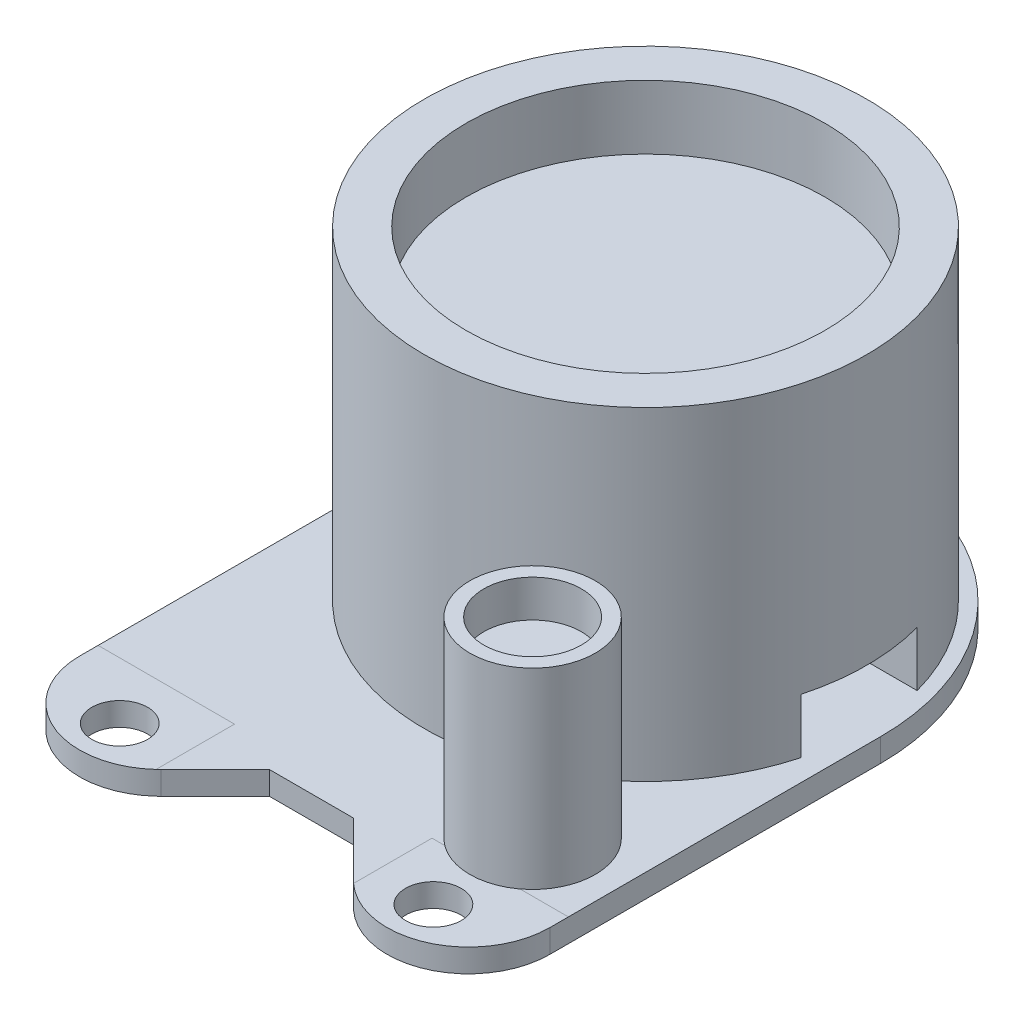
SolidWorks part; units mm, degrees
ref_plane "Front" through (0, 0, 0) normal (0, 0, 1) x (1, 0, 0)
ref_plane "Top" through (0, 0, 0) normal (0, 1, 0) x (1, 0, 0)
ref_plane "Right" through (0, 0, 0) normal (1, 0, 0) x (0, 0, -1)
sketch "Sketch1" plane through (0, 0, 0) normal (0, 1, 0) x (1, 0, 0)
  line L0 (-10.12, 0) -> (-10.12, -14.24)
  line L1 (10.12, 0) -> (10.12, -14.24)
  line L2 (-6.62, -17.74) -> (6.62, -17.74) construction
  line L3 (0, -0.8108) -> (0, -50000.8108) construction
  line L4 (-1.8103, -14.38) -> (1.8103, -14.38)
  line L5 (-4.1451, -16.7149) -> (-1.8103, -14.38)
  line L6 (1.8103, -14.38) -> (4.1451, -16.7149)
  arc A0 (10.12, 0) -> (-10.12, 0) centre (0, 0) ccw
  circle A1 centre (-6.75, -15.88) radius 1.2
  circle A2 centre (6.75, -15.88) radius 1.2
  arc A3 (-4.1451, -16.7149) -> (-10.12, -14.24) centre (-6.62, -14.24) cw
  arc A4 (4.1451, -16.7149) -> (10.12, -14.24) centre (6.62, -14.24) ccw
  point P14 (0, 0)
  point P19 (-6.1206, -18.7584)
  dimension "D1" = 20.24
  dimension "D2" = 27.86
  dimension "D3" = 2.4
  dimension "D4" = 13.5
  dimension "D7" = 26
  dimension "D6" = 0.66
  dimension "D8" = 3.5
  dimension "D9" = 3.5
  dimension "D5" = 24.5
  dimension "D10" = 45
extrude "Boss-Extrude1" add sketch "Sketch1" along normal blind 1
sketch "Sketch2" plane through (0, 1, 0) normal (0, 1, 0) x (1, 0, 0)
  line L0 (0, 0) -> (0, -50000) construction
  line L1 (0, 0) -> (50000, 0) construction
  line L3 (10.12, -14.24) -> (10.12, 0) construction
  line L4 (-4.25, -13.44) -> (-10.12, -13.44)
  line L5 (10.12, -14.24) -> (10.12, -13.44)
  line L6 (4.25, -13.44) -> (4.25, -16.8155)
  line L7 (4.25, -13.44) -> (10.12, -13.44)
  line L8 (-4.25, -13.44) -> (-4.25, -16.8155)
  line L9 (-10.12, -14.24) -> (-10.12, -13.44)
  arc A0 (4.1451, -16.7149) -> (10.12, -14.24) centre (6.62, -14.24) ccw construction
  arc A1 (4.25, -16.8155) -> (10.12, -14.24) centre (6.62, -14.24) ccw
  arc A2 (-4.25, -16.8155) -> (-10.12, -14.24) centre (-6.62, -14.24) cw
  dimension "D2" = 4.3
  dimension "D1" = 8.5
split line "Split Line1"
sketch "Sketch3" plane through (0, 0, 0) normal (0, -1, 0) x (1, 0, 0)
  line L0 (0, 0) -> (50000, 0) construction
  line L1 (0, 0) -> (3.75, 0) construction
  line L2 (0, 0) -> (2.6517, -2.6517) construction
  circle A0 centre (0, 0) radius 4.25
  circle A1 centre (0, 0) radius 3.75 construction
  circle A3 centre (3.75, 0) radius 0.15
  circle A4 centre (2.6517, -2.6517) radius 0.15
  circle A5 centre (0, -3.75) radius 0.15
  circle A6 centre (-2.6517, -2.6517) radius 0.15
  circle A7 centre (-3.75, 0) radius 0.15
  circle A8 centre (-2.6517, 2.6517) radius 0.15
  circle A9 centre (0, 3.75) radius 0.15
  circle A10 centre (2.6517, 2.6517) radius 0.15
  point P4 (0, 0)
  dimension "D1" = 8.5
  dimension "D2" = 7.5
  dimension "D3" = 0.3
  dimension "D5" = 45
  dimension "D4" = 8
split line "Split Line2"
sketch "Sketch4" plane through (0, 1, 0) normal (0, 1, 0) x (1, 0, 0)
  circle A0 centre (0, 0) radius 9.525
  circle A1 centre (0, 0) radius 7.725
  point P2 (0, 0)
  dimension "D1" = 19.05
  dimension "D2" = 1.8
extrude "Boss-Extrude2" add sketch "Sketch4" along normal blind 13.94 separate body
sketch "Sketch5" plane through (0, 0, 0) normal (1, 0, 0) x (0, 0, -1)
  line L0 (0, 11.4963) -> (0, -49988.5037) construction
  line L2 (0, 14.94) -> (0, 1) construction
  line L3 (-13.44, 1) -> (0, 1) construction
  line L4 (-2.5, 1) -> (2.5, 1)
  line L5 (-2.5, 1) -> (-2.5, 3.36)
  line L6 (-2.5, 3.36) -> (2.5, 3.36)
  line L7 (2.5, 1) -> (2.5, 3.36)
  dimension "D1" = 5
  dimension "D2" = 2.36
extrude "Cut-Extrude1" cut sketch "Sketch5" against normal through all both and the other way through all
sketch "Sketch6" plane through (0, 14.94, 0) normal (0, 1, 0) x (1, 0, 0)
  circle A0 centre (0, 0) radius 7.725 construction
  circle A1 centre (0, 0) radius 7.725
extrude "Boss-Extrude3" add sketch "Sketch6" against normal up to surface (11.58 mm away) from offset 2.75 separate body up to face at (-8.4376, 3.36, 0) offset against normal yes
sketch "Sketch7" plane through (0, 1, 0) normal (0, 1, 0) x (1, 0, 0)
  line L0 (10.12, -13.44) -> (10.12, 0) construction
  circle A0 centre (6.42, -11.28) radius 2.7
  arc A1 (4.25, -16.8155) -> (10.12, -14.24) centre (6.62, -14.24) ccw construction
  dimension "D1" = 5.4
  dimension "D2" = 3.7
  dimension "D3" = 3.76
extrude "Extrude-Thin1" add sketch "Sketch7" along normal blind 8.25 separate body thin thin type one direction reverse wall 0.6
sketch "Sketch8" plane through (0, 9.25, 0) normal (0, 1, 0) x (1, 0, 0)
  circle A0 centre (6.42, -11.28) radius 2.1 construction
  circle A3 centre (6.42, -11.28) radius 2.1
extrude "Boss-Extrude4" add sketch "Sketch8" against normal up to surface (8.25 mm away) from offset 1.6 up to face at (0, 1, 11.6218) offset against normal yes
sketch "Sketch9" plane through (0, 1, 0) normal (0, -1, 0) x (1, 0, 0)
  circle A0 centre (0, 0) radius 4
  dimension "D1" = 8
extrude "Cut-Extrude2" cut sketch "Sketch9" against normal blind 6.45
fillet "Fillet1" radius 4 1 edges at (0, 7.45, -4)
sketch "Sketch10" plane through (0, 1, 0) normal (0, -1, 0) x (1, 0, 0)
  line L0 (7.3093, -2.5) -> (9.1911, -2.5) construction
  line L1 (7.3093, 2.5) -> (9.1911, 2.5) construction
  line L2 (-7.3093, -2.5) -> (-3.1225, -2.5)
  line L3 (-7.3093, 2.5) -> (-3.1225, 2.5)
  line L4 (3.1225, 2.5) -> (7.3093, 2.5)
  line L5 (3.1225, -2.5) -> (7.3093, -2.5)
  arc A0 (-7.3093, -2.5) -> (7.3093, -2.5) centre (0, 0) ccw construction
  arc A1 (7.3093, 2.5) -> (-7.3093, 2.5) centre (0, 0) ccw construction
  arc A2 (-7.3093, -2.5) -> (7.3093, -2.5) centre (0, 0) ccw
  arc A3 (7.3093, 2.5) -> (-7.3093, 2.5) centre (0, 0) ccw
  circle A4 centre (0, 0) radius 4 construction
  arc A5 (-3.1225, -2.5) -> (3.1225, -2.5) centre (0, 0) ccw
  arc A6 (3.1225, 2.5) -> (-3.1225, 2.5) centre (0, 0) ccw
extrude "Boss-Extrude5" add sketch "Sketch10" against normal up to surface (2.36 mm away) up to face at (0, 3.36, 4)
